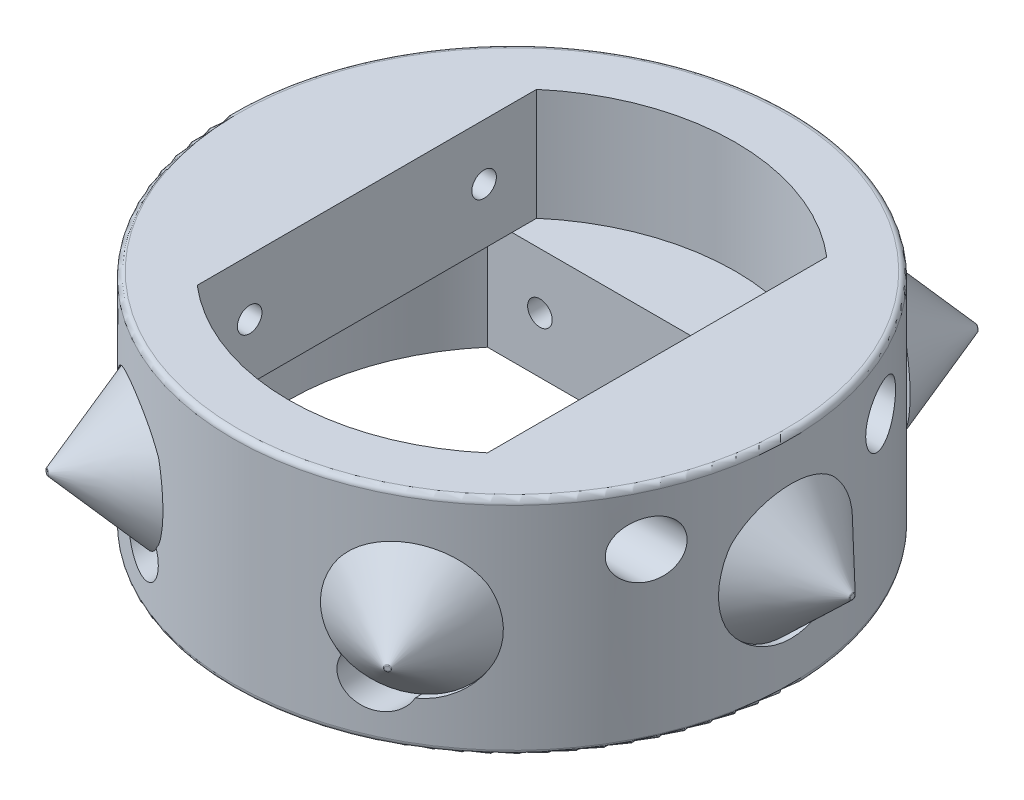
SolidWorks part; units mm, degrees
material "ABS"
ref_plane "正面" through (0, 0, 0) normal (0, 0, 1) x (1, 0, 0)
ref_plane "平面" through (0, 0, 0) normal (0, 1, 0) x (1, 0, 0)
ref_plane "右側面" through (0, 0, 0) normal (1, 0, 0) x (0, 0, -1)
sketch "ｽｹｯﾁ1" plane through (0, 0, 0) normal (0, 1, 0) x (1, 0, 0)
  circle A0 centre (0, 0) radius 25
  circle A1 centre (0, 0) radius 20
  dimension "D1" = 40
  dimension "D2" = 50
extrude "ﾎﾞｽ - 押し出し1" add sketch "ｽｹｯﾁ1" along normal blind 10 and the other way blind 10
fillet "ﾌｨﾚｯﾄ1" radius 0.5 2 edges at (0, -10, 25) (0, 10, 25)
sketch "ｽｹｯﾁ2" plane through (0, 0, 0) normal (0, 0, 1) x (1, 0, 0)
  line L0 (30.4692, 0.2795) -> (24.5, 6)
  line L1 (24.5, 6) -> (24.5, 0)
  line L2 (24.5, 0) -> (30.5, 0) construction
  line L4 (-25, 9.5) -> (25, 9.5) construction
  line L5 (-25, 9.5) -> (25, 9.5) construction
  line L6 (30.5, 0) -> (24.5, 0)
  line L7 (30.5, 0) -> (30.5, 0.2073)
  arc A0 (30.5, 0.2073) -> (30.4692, 0.2795) centre (30.4, 0.2073) ccw
  point P4 (30.5, 0.25)
  dimension "D5" = 0.1
  dimension "D1" = 0.5
  dimension "D2" = 6
  dimension "D3" = 6
  dimension "D4" = 0.25
revolve "回転1" add sketch "ｽｹｯﾁ2" angle 360 about L6 region at (26.58, 2.0034, 0) other way angle 360
ref_axis "軸1" through (0, -10, 0) along (0, 1, 0)
pattern_circular "円形ﾊﾟﾀｰﾝ5" count 6 over 360 about axis through (0, -10, 0) along (0, 1, 0) of bodies 102
sketch "ｽｹｯﾁ3" plane through (-12.25, 0, 21.2176) normal (0.5, 0, -0.866) x (-0.866, 0, -0.5)
  circle A0 centre (0, 0) radius 4.25
  dimension "D1" = 8.5
extrude "ｶｯﾄ - 押し出し1" cut sketch "ｽｹｯﾁ3" against normal blind 10
pattern_circular "円形ﾊﾟﾀｰﾝ6" count 6 over 360 about axis through (0, -10, 0) along (0, 1, 0) of "ｶｯﾄ - 押し出し1"
sketch "ｽｹｯﾁ4" plane through (0, 0, 0) normal (0, -1, 0) x (1, 0, 0)
  line L0 (-13, 15.1987) -> (-13, -15.1987)
  line L1 (13, 15.1987) -> (13, -15.1987)
  arc A1 (-13, 15.1987) -> (-13, -15.1987) centre (0, 0) ccw
  arc A2 (13, -15.1987) -> (13, 15.1987) centre (0, 0) ccw
  circle A3 centre (0, 0) radius 20 construction
  dimension "D1" = 13
  dimension "D2" = 13
extrude "ﾎﾞｽ - 押し出し2" add sketch "ｽｹｯﾁ4" against normal up to surface (10 mm away) up to face at (0, 10, 24.5)
sketch "ｽｹｯﾁ5" plane through (13, 0, 0) normal (-1, 0, 0) x (0, 0, 1)
  line L0 (15.1987, 5) -> (-15.1987, 5) construction
  line L1 (24.5, 10) -> (-24.5, 10) construction
  line L3 (0, -11) -> (0, 11) construction
  circle A0 centre (10.5, 5) radius 1.1
  circle A1 centre (-10.5, 5) radius 1.1
  dimension "D1" = 2.2
  dimension "D2" = 10.5
  dimension "D3" = 10.5
  dimension "D4" = 5
extrude "ｶｯﾄ - 押し出し2" cut sketch "ｽｹｯﾁ5" against normal through all both and the other way through all
sketch "ｽｹｯﾁ7" plane through (0, 0, 0) normal (0, -1, 0) x (1, 0, 0)
  line L0 (15.1987, -13) -> (-15.1987, -13)
  line L3 (11, 0) -> (-11, 0) construction
  line L4 (15.1987, 13) -> (-15.1987, 13)
  circle A5 centre (0, 0) radius 20 construction
  arc A6 (15.1987, 13) -> (-15.1987, 13) centre (0, 0) ccw
  arc A7 (-15.1987, -13) -> (15.1987, -13) centre (0, 0) ccw
  dimension "D1" = 13
extrude "ﾎﾞｽ - 押し出し7" add sketch "ｽｹｯﾁ7" along normal up to surface (10 mm away) up to face at (0, -10, 24.5)
sketch "ｽｹｯﾁ8" plane through (0, 0, 13) normal (0, 0, -1) x (-1, 0, 0)
  line L0 (0, 0) -> (0, -10) construction
  line L1 (13, 0) -> (-13, 0) construction
  line L2 (-15.1987, -10) -> (15.1987, -10) construction
  line L3 (-15.1987, -5) -> (15.1987, -5) construction
  line L4 (-15.1987, -10) -> (-15.1987, 0) construction
  line L5 (15.1987, -10) -> (15.1987, 0) construction
  circle A1 centre (10.5, -5) radius 1.1
  circle A2 centre (-10.5, -5) radius 1.1
  dimension "D1" = 2.2
  dimension "D2" = 10.5
extrude "ｶｯﾄ - 押し出し3" cut sketch "ｽｹｯﾁ8" against normal through all and the other way through all
sketch "ｽｹｯﾁ9" plane through (-24.5, 0, 0) normal (1, 0, 0) x (0, 0, -1)
  circle A0 centre (0, 0) radius 6 construction
  circle A1 centre (0, 0) radius 6
extrude "ｶｯﾄ - 押し出し4" cut sketch "ｽｹｯﾁ9" against normal through all
pattern_circular "円形ﾊﾟﾀｰﾝ7" count 6 over 360 about axis through (0, -10, 0) along (0, 1, 0) of "ｶｯﾄ - 押し出し4"
ref_plane "平面1" through (0, 0, 25) normal (0, 0, 1) x (1, 0, 0)
sketch "ｽｹｯﾁ11" plane through (0, 0, 25) normal (0, 0, 1) x (1, 0, 0)
  circle A0 centre (10.5, -5) radius 2.5
  circle A1 centre (-10.5, -5) radius 2.5
  arc A2 (11.1734, -5.8698) -> (9.4001, -5.0171) centre (10.5, -5) ccw construction
  arc A3 (-9.4001, -5.0171) -> (-11.1734, -5.8698) centre (-10.5, -5) ccw construction
  dimension "D1" = 5
extrude "ｶｯﾄ - 押し出し5" cut sketch "ｽｹｯﾁ11" against normal blind 8
mirror "ﾐﾗｰ1" about plane through (0, 0, 0) normal (0, 0, 1) of "ｶｯﾄ - 押し出し5"
ref_plane "平面2" through (25, 0, 0) normal (1, 0, 0) x (0, 0, -1)
sketch "ｽｹｯﾁ12" plane through (25, 0, 0) normal (1, 0, 0) x (0, 0, -1)
  circle A0 centre (10.5, 5) radius 2.5
  circle A1 centre (-10.5, 5) radius 2.5
  circle A2 centre (10.5, 5) radius 1.1 construction
  circle A3 centre (-10.5, 5) radius 1.1 construction
  dimension "D1" = 5
extrude "ｶｯﾄ - 押し出し6" cut sketch "ｽｹｯﾁ12" against normal blind 8
mirror "ﾐﾗｰ2" about plane through (0, 0, 0) normal (1, 0, 0) of "ｶｯﾄ - 押し出し6"
